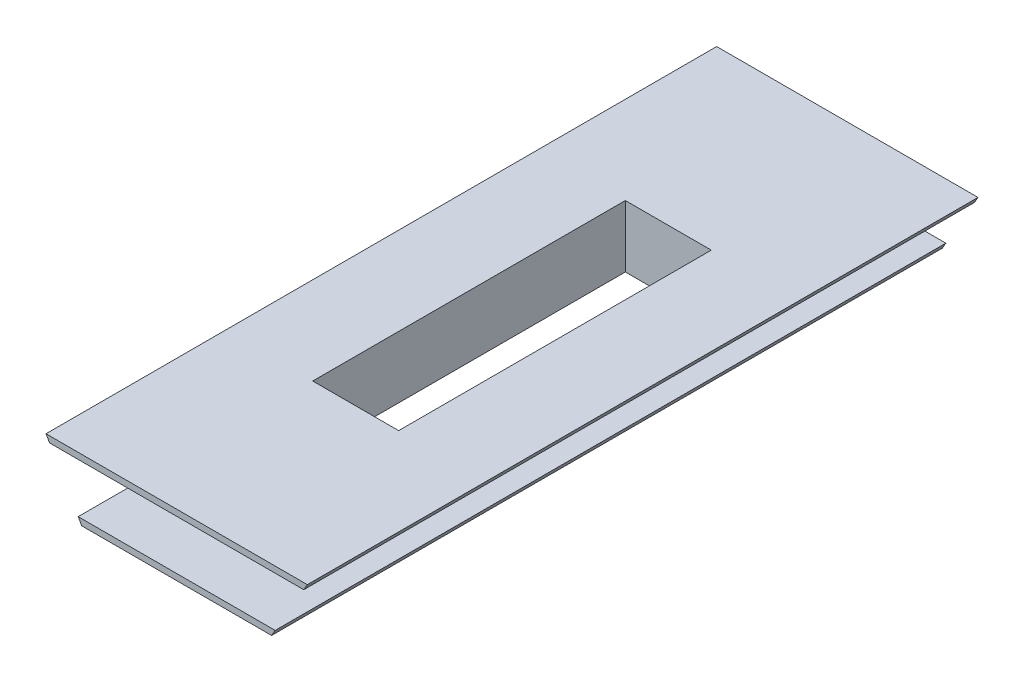
SolidWorks part; units mm, degrees
ref_plane "Front Plane" through (0, 0, 0) normal (0, 0, 1) x (1, 0, 0)
ref_plane "Top Plane" through (0, 0, 0) normal (0, 1, 0) x (1, 0, 0)
ref_plane "Right Plane" through (0, 0, 0) normal (1, 0, 0) x (0, 0, -1)
sketch "Sketch2" plane through (0, 0, 0) normal (0, 0, 1) x (1, 0, 0)
  line L0 (9.2, 0) -> (-9.2, 0)
  line L1 (-9.2, 0) -> (-9.5464, 0.6)
  line L3 (9.2, 0) -> (9.5464, 0.6)
  line L4 (-12.6641, 6) -> (12.6641, 6)
  line L5 (-11.6249, 5.4) -> (-4.7641, 5.4)
  line L7 (8.8536, 0.6) -> (4.7641, 0.6)
  line L9 (4.7641, 5.4) -> (11.6249, 5.4)
  line L11 (12.3177, 5.4) -> (12.6641, 6)
  line L13 (9.2, 0) -> (12.6641, 6) construction
  line L14 (-11.6249, 5.4) -> (-12.3177, 5.4)
  line L15 (11.6249, 5.4) -> (12.3177, 5.4)
  line L16 (8.8536, 0.6) -> (9.5464, 0.6)
  line L17 (-8.8536, 0.6) -> (-9.5464, 0.6)
  line L18 (-12.3177, 5.4) -> (-12.6641, 6)
  line L19 (-9.2, 0) -> (-12.6641, 6) construction
  line L20 (8.8536, 0.6) -> (11.6249, 5.4) construction
  line L21 (-8.8536, 0.6) -> (-11.6249, 5.4) construction
  line L22 (0, 5.5055) -> (0, 11.4768) construction
  line L23 (-11.6249, 5.4) -> (11.6249, 5.4) construction
  line L24 (-4.7641, 0.6) -> (-8.8536, 0.6)
  line L25 (8.8536, 0.6) -> (-8.8536, 0.6) construction
  line L56 (-4.7641, 5.4) -> (-4.7641, 0.6)
  line L57 (4.7641, 0.6) -> (4.7641, 5.4)
  point P14 (0, 3)
  point P21 (4.1641, 3)
  point P24 (-4.1641, 3)
  dimension "D1" = 120
  dimension "D3" = 6
  dimension "D5" = 120
  dimension "D6" = 25.3282
  dimension "D4" = 0.6
extrude "Boss-Extrude1" add sketch "Sketch2" along normal blind 65
sketch "Sketch5" plane through (0, 0, 0) normal (0, 0, -1) x (-1, 0, 0)
  line L0 (4.7641, 0.6) -> (-4.7641, 0.6)
  line L1 (-4.7641, 0.6) -> (-4.7641, 5.4)
  line L2 (-4.7641, 5.4) -> (4.7641, 5.4)
  line L3 (4.7641, 5.4) -> (4.7641, 0.6)
extrude "Cut-Extrude3" cut sketch "Sketch5" against normal blind 16.75
sketch "Sketch6" plane through (0, 0, 65) normal (0, 0, 1) x (1, 0, 0)
  line L0 (4.7641, 0.6) -> (-4.7641, 0.6)
  line L1 (-4.7641, 0.6) -> (-4.7641, 5.4)
  line L2 (-4.7641, 5.4) -> (4.7641, 5.4)
  line L3 (4.7641, 5.4) -> (4.7641, 0.6)
extrude "Cut-Extrude4" cut sketch "Sketch6" against normal blind 16.75
sketch "Sketch7" plane through (0, 6, 0) normal (0, 1, 0) x (1, 0, 0)
  line L0 (4.1641, -17.95) -> (4.1641, -47.05)
  line L1 (4.1641, -17.35) -> (-4.1641, -17.35)
  line L3 (4.1641, -47.65) -> (-4.1641, -47.65)
  line L6 (-4.1641, -17.95) -> (-4.1641, -47.05)
  line L8 (4.1641, -17.95) -> (-4.1641, -17.95) construction
  line L9 (4.1641, -47.05) -> (-4.1641, -47.05) construction
  line L10 (4.1641, -47.05) -> (4.1641, -47.65)
  line L11 (-4.1641, -47.05) -> (-4.1641, -47.65)
  line L12 (4.1641, -17.95) -> (4.1641, -17.35)
  line L13 (-4.1641, -17.95) -> (-4.1641, -17.35)
  line L14 (4.7641, -47.65) -> (-4.7641, -47.65) construction
  line L15 (4.7641, -17.35) -> (4.7641, -47.65) construction
  line L16 (-4.7641, -17.35) -> (-4.7641, -47.65) construction
  line L17 (4.7641, -17.35) -> (-4.7641, -17.35) construction
  dimension "D1" = 0.6
extrude "Cut-Extrude5" cut sketch "Sketch7" against normal through all both and the other way through all contours L0 L10 L3 L11 L6 L13 L1 L12
